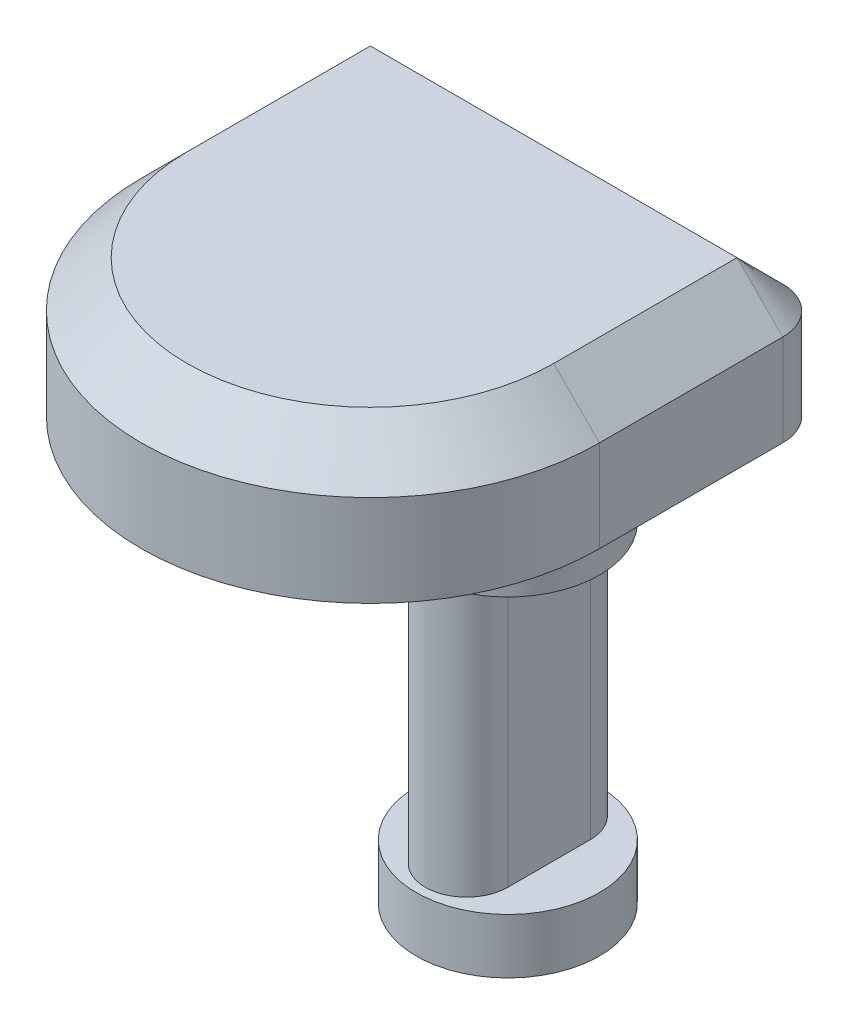
SolidWorks part; units mm, degrees
ref_plane "前视基准面" through (0, 0, 0) normal (0, 0, 1) x (1, 0, 0)
ref_plane "上视基准面" through (0, 0, 0) normal (0, 1, 0) x (1, 0, 0)
ref_plane "右视基准面" through (0, 0, 0) normal (1, 0, 0) x (0, 0, -1)
other "Configuration Table"
sketch "草图1" plane through (0, 0, 0) normal (0, 1, 0) x (1, 0, 0)
  line L0 (0, 0.9) -> (0, -0.9) construction
  line L5 (0.9, 0.9) -> (0.9, -0.9)
  line L6 (-0.9, 0.9) -> (-0.9, -0.9)
  arc A0 (0.9, 0.9) -> (-0.9, 0.9) centre (0, 0.9) ccw
  arc A1 (-0.9, -0.9) -> (0.9, -0.9) centre (0, -0.9) ccw
  point P2 (0, 0)
extrude "凸台-拉伸1" add sketch "草图1" along normal blind 8
sketch "草图2" plane through (0, 8, 0) normal (0, 1, 0) x (1, 0, 0)
  circle A0 centre (0, 0) radius 2
extrude "凸台-拉伸2" add sketch "草图2" against normal blind 1
sketch "草图3" plane through (0, 0, 0) normal (0, -1, 0) x (1, 0, 0)
  circle A0 centre (0, 0) radius 2
extrude "凸台-拉伸3" add sketch "草图3" against normal blind 1 and the other way blind 0.2
sketch "草图6" plane through (0, 8, 0) normal (0, 1, 0) x (1, 0, 0)
  line L0 (0, -0.9) -> (0, 0.9) construction
  line L1 (-0.9, -0.9) -> (-0.9, 0.9)
  line L2 (0.9, -0.9) -> (0.9, 0.9)
  arc A0 (-0.9, -0.9) -> (0.9, -0.9) centre (0, -0.9) ccw
  arc A1 (0.9, 0.9) -> (-0.9, 0.9) centre (0, 0.9) ccw
  point P2 (0, 0)
extrude "凸台-拉伸4" add sketch "草图6" along normal blind 2.5
sketch "草图7" plane through (0, 10.5, 0) normal (0, 1, 0) x (1, 0, 0)
  line L2 (-5, -3) -> (-5, 1)
  line L3 (-4, 2) -> (4, 2)
  line L4 (5, -3) -> (5, 1)
  line L5 (-5, -8) -> (5, 2) construction
  line L6 (-5, 2) -> (5, -8) construction
  arc A1 (-5, -3) -> (5, -3) centre (0, -3) ccw
  arc A2 (4, 2) -> (5, 1) centre (4, 1) cw
  arc A3 (-5, 1) -> (-4, 2) centre (-4, 1) cw
  point P0 (0, 0)
  dimension "D1" = 1
extrude "凸台-拉伸5" add sketch "草图7" along normal blind 3
chamfer "倒角1" distance 1 angle 45 6 edges at (0, 13.5, -2) (-4.7071, 13.5, -1.7071) (4.7071, 13.5, -1.7071) (-5, 13.5, 1) (5, 13.5, 1) (0, 13.5, 8)
sketch "草图8" plane through (0, -0.2, 0) normal (0, -1, 0) x (1, 0, 0)
  line L0 (-0.4, 0) -> (0.4, 0) construction
  line L1 (-0.4, 1.2) -> (0.4, 1.2)
  line L2 (-0.4, -1.2) -> (0.4, -1.2)
  arc A0 (-0.4, 1.2) -> (-0.4, -1.2) centre (-0.4, 0) ccw
  arc A1 (0.4, -1.2) -> (0.4, 1.2) centre (0.4, 0) ccw
  point P2 (0, 0)
extrude "切除-拉伸1" cut sketch "草图8" against normal blind 0.2
